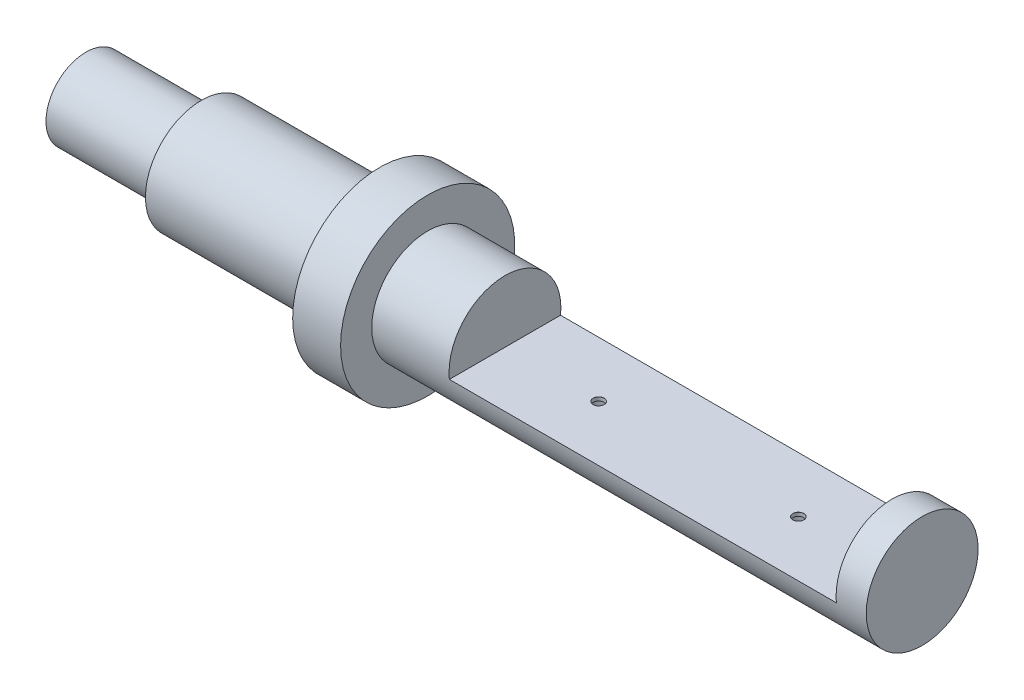
SolidWorks part; units mm, degrees
ref_plane "Front Plane" through (0, 0, 0) normal (0, 0, 1) x (1, 0, 0)
ref_plane "Top Plane" through (0, 0, 0) normal (0, 1, 0) x (1, 0, 0)
ref_plane "Right Plane" through (0, 0, 0) normal (1, 0, 0) x (0, 0, -1)
sketch "Sketch1" plane through (0, 0, 0) normal (0, 1, 0) x (1, 0, 0)
  line L0 (0, 0) -> (418.7, 0)
  line L1 (418.7, 0) -> (418.7, 28)
  line L2 (418.7, 28) -> (171.1, 28)
  line L3 (171.1, 28) -> (171.1, 43.6)
  line L4 (171.1, 43.6) -> (147.1, 43.6)
  line L5 (147.1, 43.6) -> (147.1, 28)
  line L6 (147.1, 28) -> (57.8, 28)
  line L7 (57.8, 28) -> (57.8, 20)
  line L8 (57.8, 20) -> (0, 20)
  line L9 (0, 20) -> (0, 0)
  point P2 (28.9, 20)
  dimension "D1" = 20
  dimension "D2" = 28
  dimension "D3" = 43.6
  dimension "D4" = 247.6
  dimension "D5" = 89.3
  dimension "D6" = 24
  dimension "D7" = 28.9
revolve "Revolve1" add sketch "Sketch1" angle 360 about L0
sketch "Sketch2" plane through (0, 0, 0) normal (0, 0, 1) x (1, 0, 0)
  line L0 (418.7, 28) -> (171.1, 28) construction
  line L1 (209.8, 28) -> (403.6, 28)
  line L2 (209.8, 28) -> (209.8, -3.1)
  line L3 (209.8, -3.1) -> (403.6, -3.1)
  line L4 (403.6, 28) -> (403.6, -3.1)
  line L5 (418.7, -28) -> (418.7, 28) construction
  dimension "D1" = 15.1
  dimension "D2" = 31.1
  dimension "D3" = 193.8
extrude "Cut-Extrude1" cut sketch "Sketch2" against normal through all both and the other way through all
sketch "Sketch3" plane through (0, -3.1, 0) normal (0, 1, 0) x (1, 0, 0)
  line L0 (209.8, 27.8279) -> (209.8, -27.8279) construction
  point P0 (256.7, 0)
  point P2 (356.7, 0)
  point P12 (340.6491, 1.5792)
  dimension "D1" = 100
  dimension "D2" = 46.9
hole_wizard "CBORE for M2.5 Cheese Head Screw1" positions "Sketch3" profile "Sketch4" counterbore size "M2.5" standard "AS" end condition up to next
sketch "Sketch4" plane through (256.7, -3.1, 0) normal (1, 0, 0) x (0, 0, 1)
  line L0 (0, 0) -> (0, 24.9)
  line L1 (0, 24.9) -> (6.25, 24.9)
  line L3 (6.25, 24.9) -> (6.25, 1.8)
  line L4 (2.75, 1.8) -> (6.25, 1.8)
  line L5 (2.75, 1.8) -> (2.75, 0.025)
  line L6 (2.75, 0.025) -> (2.775, 0)
  line L7 (2.775, 0) -> (0, 0)
  line L8 (-2.75, 0.025) -> (-2.775, 0) construction
  line L11 (0, -6.35) -> (0, 107.95) construction
  dimension "Thru Hole Dia." = 12.5
  dimension "Thru Hole Depth" = 24.9
  dimension "C'Bore Dia." = 5.5
  dimension "C'Bore Depth" = 1.8
  dimension "Near C'Sink Dia." = 5.55
  dimension "Near C'Sink Angle" = 90
